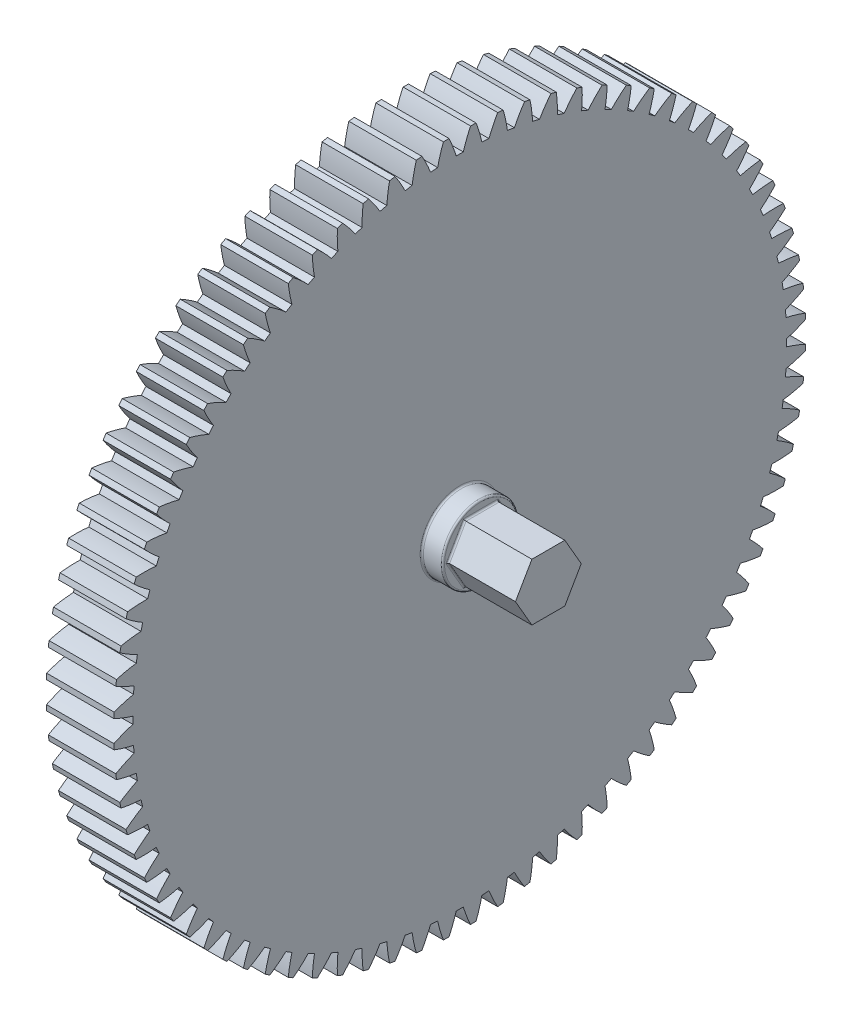
SolidWorks part; units mm, degrees
ref_plane "Plane1" through (0, 0, 0) normal (0, 0, 1) x (1, 0, 0)
ref_plane "Plane2" through (0, 0, 0) normal (0, 1, 0) x (1, 0, 0)
ref_plane "Plane3" through (0, 0, 0) normal (1, 0, 0) x (0, 0, -1)
sketch "HoldingSke" plane through (0, 0, 0) normal (0, 1, 0) x (1, 0, 0)
  line L0 (0, 0) -> (0.1736, -0.9848)
  line L1 (-15, 0) -> (100, 0) construction
  line L2 (0, 0) -> (-2.1039, 2.3779)
  line L3 (0, 0) -> (-11.863, 4.5341)
  line L4 (0, 0) -> (1.4996, 8.5048)
  line L5 (0, 0) -> (-46.8476, -17.4728)
  line L6 (0, 0) -> (-6.6317, -4.4744)
  line L7 (-2.1039, 2.3779) -> (8.6586, 51.2059)
  line L8 (-76.2, 54.61) -> (-76.1, 54.61)
  line L9 (-71.009, 38.7566) -> (-53.1078, 45.2721)
  line L10 (-76.2, 71.12) -> (104.1128, 71.12)
  line L11 (0, 0) -> (-8, 0)
  line L12 (-76.2, 101.6) -> (-76.162, 101.6)
  line L13 (24.9733, 27.94) -> (52.9518, 28.4284)
  line L14 (24.9733, 27.94) -> (24.9743, 27.94)
  line L15 (24.9733, 27.94) -> (100.4006, 29.5858)
  line L16 (-63.627, -1) -> (-12.827, -1)
  circle A0 centre (0, 0) radius 0.4
  circle A1 centre (0, 0) radius 37.5
  circle A2 centre (0, 0) radius 37.5
  circle A3 centre (0, 0) radius 0.4
  dimension "Num_teeth" = 80
  dimension "Pitch_radius" = 180.3128
  dimension "Width" = 8
  dimension "Thickness" = 8
sketch "BasProSke" plane through (0, 0, 0) normal (0, 1, 0) x (1, 0, 0)
  line L0 (-10, 0) -> (60, 0) construction
  line L1 (0, 0) -> (0, 41)
  line L2 (0, 0) -> (8, 0)
  line L3 (8, 0) -> (8, 41)
  line L4 (8, 41) -> (0, 41)
  dimension "Thickness" = 8
  dimension "Diameter" = 82
revolve "Base-Revolve" add sketch "BasProSke" angle 360 about L0
sketch "TooCutSke" plane through (0, 0, 0) normal (1, 0, 0) x (0, 0, -1)
  line L1 (0, 0) -> (0, 107) construction
  line L2 (0, 0) -> (-0.8518, 39.9909) construction
  line L3 (0, 0) -> (-3.1403, 79.9254) construction
  line L4 (-0.8518, 39.9909) -> (-1.5701, 39.9627) construction
  arc A0 (0.4206, 38.7467) -> (-0.4206, 38.7467) centre (0, 0) ccw
  arc A1 (1.2919, 41.0051) -> (-1.2919, 41.0051) centre (0, 0) ccw
  circle A2 centre (0, 0) radius 40 construction
  circle A3 centre (0, 0) radius 37.5877 construction
  arc A4 (-0.4206, 38.7467) -> (-1.2919, 41.0051) centre (-15.7409, 34.133) ccw
  arc A5 (1.2919, 41.0051) -> (0.4206, 38.7467) centre (15.7409, 34.133) ccw
extrude "ToothCut" cut sketch "TooCutSke" along normal through all
fillet "Breaks" [suppressed] radius 0.02 tangent propagation no
fillet "RootFillets" [suppressed] radius 0.251
pattern_circular "TeethCuts" count 80 every 4.5 about axis through (-10, 0, 0) along (1, 0, 0) of "ToothCut", "RootFillets", "Breaks"
sketch "HubNeaOneSke" plane through (0, 0, 0) normal (-1, 0, 0) x (0, 0, 1)
  circle A0 centre (0, 0) radius 37.5
  dimension "Diameter" = 75
extrude "HubNearOne" [suppressed] add sketch "HubNeaOneSke" along normal blind 42.0001
sketch "HubNeaBotSke" plane through (0, 0, 0) normal (-1, 0, 0) x (0, 0, 1)
  circle A0 centre (0, 0) radius 37.5
  dimension "Diameter" = 75
extrude "HubNearBoth" [suppressed] add sketch "HubNeaBotSke" along normal blind 21
ref_plane "FarPln" through (8, 0, 0) normal (1, 0, 0) x (0, 0, -1)
sketch "HubFarSke" plane through (8, 0, 0) normal (1, 0, 0) x (0, 0, -1)
  circle A0 centre (0, 0) radius 37.5
  dimension "Diameter" = 75
extrude "HubFar" [suppressed] add sketch "HubFarSke" along normal blind 21
sketch "BorSke" plane through (0, 0, 0) normal (1, 0, 0) x (0, 0, -1)
  circle A0 centre (0, 0) radius 0.4
  dimension "Diameter" = 0.8
extrude "Bore" cut sketch "BorSke" along normal mid plane 100.0001
sketch "KeySke" plane through (0, 0, 0) normal (1, 0, 0) x (0, 0, -1)
  line L0 (-0.05, 0) -> (-0.05, 0.5)
  line L1 (-0.05, 0.5) -> (0.05, 0.5)
  line L2 (0.05, 0.5) -> (0.05, 0)
  line L3 (0, 0) -> (0, 34) construction
  line L4 (-0.05, 0) -> (0.05, 0)
  dimension "Width" = 0.1
extrude "Keyway" [suppressed] cut sketch "KeySke" along normal mid plane 100.0001
pattern_circular "Keyway2" [suppressed] count 2 every 90 about axis through (-10, 0, 0) along (1, 0, 0) reverse direction yes
sketch "Croquis1" plane through (8, 0, 0) normal (1, 0, 0) x (0, 0, -1)
  circle A2 centre (0, 0) radius 4.5
  dimension "D1" = 9
extrude "Saliente-Extruir1" add sketch "Croquis1" along normal blind 2.5
sketch "Croquis2" plane through (10.5, 0, 0) normal (1, 0, 0) x (0, 0, -1)
  line L1 (3.9, 0) -> (1.95, 3.3775)
  line L2 (1.95, 3.3775) -> (-1.95, 3.3775)
  line L3 (-1.95, 3.3775) -> (-3.9, 0)
  line L4 (-3.9, 0) -> (-1.95, -3.3775)
  line L5 (-1.95, -3.3775) -> (1.95, -3.3775)
  line L6 (1.95, -3.3775) -> (3.9, 0)
  circle A0 centre (0, 0) radius 3.3775 construction
  point P1 (0, 0)
  point P10 (0, 0)
  dimension "D1" = 7.8
extrude "Saliente-Extruir2" add sketch "Croquis2" along normal blind 8
fillet "Redondeo1" radius 0.2 8 edges at (10.5, 0, -4.5) (10.5, 1.6887, -2.925) (10.5, 3.3775, 0) (10.5, 1.6887, 2.925) (10.5, -1.6887, 2.925) (10.5, -3.3775, 0) (10.5, -1.6887, -2.925) (8, 0, 4.5)
equation "' \"Module@HoldingSke\" = 6.35"
equation "' \"Num_teeth@HoldingSke\" = 12"
equation "' \"Ap@HoldingSke\" =  20"
equation "' \"Ap@HoldingSke\" = 20"
equation "' \"Width@HoldingSke\" = 0.5 * 25.4"
equation "' \"Hub_dia@HoldingSke\"= 1 * 25.4"
equation "' \"Hub_dia@HoldingSke\" = 1 * 25.4"
equation "' \"Overall_len@HoldingSke\" = 1.0 * 25.4"
equation "' \"Bore@HoldingSke\" = 0.75 * 25.4"
equation "' \"T_dim@HoldingSke\" = 0.1 * 25.4"
equation "' \"Width@KeySke\" = 0.25 * 25.4"
equation "' \"Show_teeth@HoldingSke\" = 13"
equation "' \"Backlash@HoldingSke\" = 0.009 * 25.4"
equation "' \"Addendum_fac@HoldingSke\" = 1.0"
equation "' \"Dedendum_fac@HoldingSke\" = 1.25"
equation "' \"Dedendum_add@HoldingSke\" = 0.00005 * 25.4"
equation "' \"Clearance_fac@HoldingSke\" = 0.25"
equation "\"Pitch@HoldingSke\" = 1 / \"Module@HoldingSke\""
equation "\"Overcut_dia@TooCutSke\" = (\"Num_teeth@HoldingSke\" + 2 * \"Addendum_fac@HoldingSke\") / \"Pitch@HoldingSke\" + 0.002 * 25.4"
equation "\"Pitch_dia@TooCutSke\" = \"Num_teeth@HoldingSke\" / \"Pitch@HoldingSke\""
equation "\"Base_dia@TooCutSke\" = \"Num_teeth@HoldingSke\" / \"Pitch@HoldingSke\" * cos((\"Ap@HoldingSke\"  * 3.14159265 / 180))"
equation "\"Root_dia@TooCutSke\" = (\"Num_teeth@HoldingSke\" + 2) / \"Pitch@HoldingSke\" - 2 * (\"Addendum_fac@HoldingSke\" + \"Dedendum_fac@HoldingSke\") / \"Pitch@HoldingSke\" - \"Dedendum_add@HoldingSke\" * 2"
equation "\"Half_ang@TooCutSke\" = 180 / \"Num_teeth@HoldingSke\""
equation "\"Half_CT@TooCutSke\" = \"Num_teeth@HoldingSke\" / \"Pitch@HoldingSke\" * sin((3.14159265 / 2 / \"Num_teeth@HoldingSke\")) / 2 - 7 * \"Backlash@HoldingSke\" / 4"
equation "\"Flank_rad@TooCutSke\" = \"Num_teeth@HoldingSke\" / \"Pitch@HoldingSke\" / 5"
equation "\"Radius@RootFillets\" = \"Clearance_fac@HoldingSke\" / \"Pitch@HoldingSke\" + \"Dedendum_add@HoldingSke\""
equation "\"Break_rad@Breaks\" = 0.02 / \"Pitch@HoldingSke\""
equation "\"Thickness@HoldingSke\" = \"Width@HoldingSke\""
equation "\"OAL@HoldingSke\" = \"Thickness@HoldingSke\""
equation "\"MHD@HoldingSke\" = (\"Num_teeth@HoldingSke\" + 2) / \"Pitch@HoldingSke\" - 2 * (\"Addendum_fac@HoldingSke\" + \"Dedendum_fac@HoldingSke\")  / \"Pitch@HoldingSke\" - \"Dedendum_add@HoldingSke\" * 2"
equation "\"MBD@HoldingSke\" = (\"Num_teeth@HoldingSke\" + 2) / \"Pitch@HoldingSke\" - 2 * (\"Addendum_fac@HoldingSke\" + \"Dedendum_fac@HoldingSke\")  / \"Pitch@HoldingSke\" - \"Dedendum_add@HoldingSke\" * 2 - 0.002 * 25.4"
equation "\"MHD@HoldingSke\" = ((sgn( \"MHD@HoldingSke\" - \"Hub_dia@HoldingSke\" )-1)*( \"MHD@HoldingSke\" - \"Hub_dia@HoldingSke\" ))/-2+ \"Hub_dia@HoldingSke\""
equation "\"MBD@HoldingSke\" = ((sgn( \"MBD@HoldingSke\" - \"Bore@HoldingSke\" )-1)*( \"MBD@HoldingSke\" - \"Bore@HoldingSke\" ))/-2+ \"Bore@HoldingSke\""
equation "\"OAL@HoldingSke\" = ((sgn( \"OAL@HoldingSke\" - \"Overall_len@HoldingSke\" )+1)*( \"OAL@HoldingSke\" - \"Overall_len@HoldingSke\" ))/2 + \"Overall_len@HoldingSke\" + 0.000002 * 25.4"
equation "\"Num_teeth@TeethCuts\" = int( \"Show_teeth@HoldingSke\" ) + 1"
equation "\"Num_teeth@TeethCuts\" = ((sgn( \"Num_teeth@TeethCuts\" - \"Num_teeth@HoldingSke\" )-1)*( \"Num_teeth@TeethCuts\" - \"Num_teeth@HoldingSke\" ))/-2+ \"Num_teeth@HoldingSke\""
equation "\"Num_teeth@TeethCuts\" = ((sgn( \"Num_teeth@TeethCuts\" - 2.0)+1)*( \"Num_teeth@TeethCuts\" - 2.0))/2 +2.0"
equation "\"Angle@TeethCuts\" = 360.0 / \"Num_teeth@HoldingSke\""
equation "\"Diameter@BasProSke\" = (\"Num_teeth@HoldingSke\" + 2 * \"Addendum_fac@HoldingSke\") / \"Pitch@HoldingSke\""
equation "\"Thickness@BasProSke\"  = \"Thickness@HoldingSke\""
equation "' \"Fillet_rad@BasProSke\" =  \"Thickness@HoldingSke\" * 0.05"
equation "' \"Fillet_rad@BasProSke\" = \"Thickness@HoldingSke\" * 0.05"
equation "\"MHD@HoldingSke\" = ((sgn( \"MHD@HoldingSke\" - \"Root_dia@TooCutSke\" )-1)*( \"MHD@HoldingSke\" - \"Root_dia@TooCutSke\" ))/-2+ \"Root_dia@TooCutSke\""
equation "\"Diameter@HubNeaOneSke\" = \"MHD@HoldingSke\""
equation "\"Length@HubNearOne\" = \"OAL@HoldingSke\" - \"Thickness@BasProSke\""
equation "\"Diameter@HubNeaBotSke\" = \"MHD@HoldingSke\""
equation "\"Length@HubNearBoth\" = ( \"OAL@HoldingSke\" - \"Thickness@BasProSke\" ) / 2.0"
equation "\"Thickness@FarPln\" = \"Thickness@BasProSke\""
equation "\"Diameter@HubFarSke\" = \"MHD@HoldingSke\""
equation "\"Length@HubFar\" = ( \"OAL@HoldingSke\" - \"Thickness@BasProSke\" ) / 2.0"
equation "\"Diameter@BorSke\" = \"MBD@HoldingSke\""
equation "\"D1@Bore\" = \"OAL@HoldingSke\" * 2.0"
equation "\"D1@Keyway\" = \"OAL@HoldingSke\" * 2.0"
equation "\"Offset@KeySke\" = \"T_dim@HoldingSke\" + \"MBD@HoldingSke\" / 2.0"
